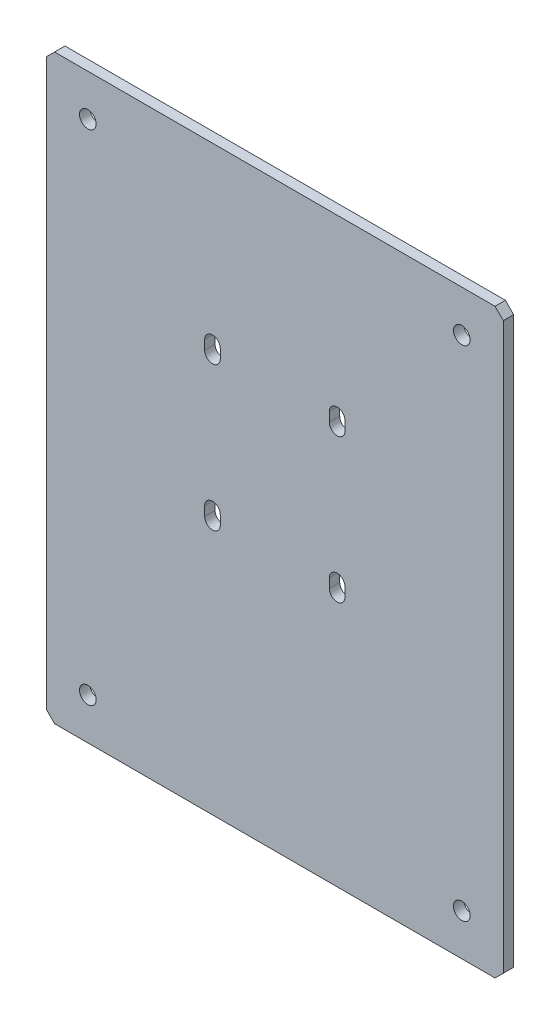
SolidWorks part; units mm, degrees
material "Acrylic (Medium-high impact)"
ref_plane "Front" through (0, 0, 0) normal (0, 0, 1) x (1, 0, 0)
ref_plane "Top" through (0, 0, 0) normal (0, 1, 0) x (1, 0, 0)
ref_plane "Right" through (0, 0, 0) normal (1, 0, 0) x (0, 0, -1)
sketch "Sketch1" plane through (0, 0, 0) normal (0, 0, 1) x (1, 0, 0)
  line L1 (0, 0) -> (139.7, 0)
  line L2 (0, 0) -> (0, 177.8)
  line L3 (0, 177.8) -> (139.7, 177.8)
  line L4 (139.7, 0) -> (139.7, 177.8)
extrude "Boss-Extrude1" add sketch "Sketch1" against normal blind 3.175
sketch "Sketch2" plane through (0, 0, 0) normal (0, 0, 1) x (1, 0, 0)
  line L0 (50.8, 121.7875) -> (50.8, 124.645) construction
  line L1 (48.4187, 121.7875) -> (48.4187, 124.645)
  line L2 (53.1813, 121.7875) -> (53.1813, 124.645)
  line L3 (50.8, 77.7875) -> (50.8, 80.645) construction
  line L4 (48.4187, 77.7875) -> (48.4187, 80.645)
  line L5 (53.1813, 77.7875) -> (53.1813, 80.645)
  line L12 (69.85, 0) -> (69.85, 21.0033) construction
  line L13 (0, 0) -> (139.7, 0) construction
  line L14 (88.9, 121.7875) -> (88.9, 124.645) construction
  line L15 (91.2813, 121.7875) -> (91.2813, 124.645)
  line L16 (86.5187, 121.7875) -> (86.5187, 124.645)
  line L17 (88.9, 77.7875) -> (88.9, 80.645) construction
  line L18 (91.2813, 77.7875) -> (91.2813, 80.645)
  line L19 (86.5187, 77.7875) -> (86.5187, 80.645)
  arc A0 (48.4187, 121.7875) -> (53.1813, 121.7875) centre (50.8, 121.7875) ccw
  arc A1 (53.1813, 124.645) -> (48.4187, 124.645) centre (50.8, 124.645) ccw
  arc A2 (48.4187, 77.7875) -> (53.1813, 77.7875) centre (50.8, 77.7875) ccw
  arc A3 (53.1813, 80.645) -> (48.4187, 80.645) centre (50.8, 80.645) ccw
  arc A8 (91.2813, 121.7875) -> (86.5187, 121.7875) centre (88.9, 121.7875) cw
  arc A9 (86.5187, 124.645) -> (91.2813, 124.645) centre (88.9, 124.645) cw
  arc A10 (91.2813, 77.7875) -> (86.5187, 77.7875) centre (88.9, 77.7875) cw
  arc A11 (86.5187, 80.645) -> (91.2813, 80.645) centre (88.9, 80.645) cw
  point P2 (50.8, 123.2162)
  point P9 (50.8, 79.2162)
  point P34 (88.9, 123.2162)
  point P41 (88.9, 79.2162)
  dimension "D2" = 7.62
  dimension "D5" = 44
  dimension "D6" = 77.7875
  dimension "D3" = 38.1
  dimension "D1" = 4.7625
extrude "Cut-Extrude1" cut sketch "Sketch2" against normal through all
sketch "Sketch5" plane through (0, 0, 0) normal (0, 0, 1) x (1, 0, 0)
  line L0 (0, 0) -> (139.7, 0) construction
  line L1 (0, 177.8) -> (0, 0) construction
  line L2 (139.7, 177.8) -> (0, 177.8) construction
  line L3 (139.7, 0) -> (139.7, 177.8) construction
  point P0 (12.7, 12.7)
  point P2 (12.7, 165.1)
  point P4 (127, 165.1)
  point P6 (127, 12.7)
  dimension "D1" = 12.7
  dimension "D2" = 12.7
  dimension "D3" = 12.7
  dimension "D4" = 12.7
hole_wizard "#10 Clearance Hole1" positions "Sketch5" profile "Sketch4" hole size "#10" standard "ANSI Inch" end condition through all
sketch "Sketch4" plane through (12.7, 12.7, 0) normal (1, 0, 0) x (0, -1, 0)
  line L0 (0, 0) -> (0, 3.175)
  line L1 (0, 3.175) -> (2.5527, 3.175)
  line L2 (2.5527, 3.175) -> (2.5527, 0)
  line L5 (2.5527, 0) -> (0, 0)
  line L11 (0, -6.35) -> (0, 107.95) construction
  dimension "Thru Hole Dia." = 5.1054
  dimension "Thru Hole Depth" = 3.175
chamfer "Chamfer1" distance 2.54 angle 45 4 edges at (0, 0, -1.5875) (139.7, 0, -1.5875) (139.7, 177.8, -1.5875) (0, 177.8, -1.5875)
